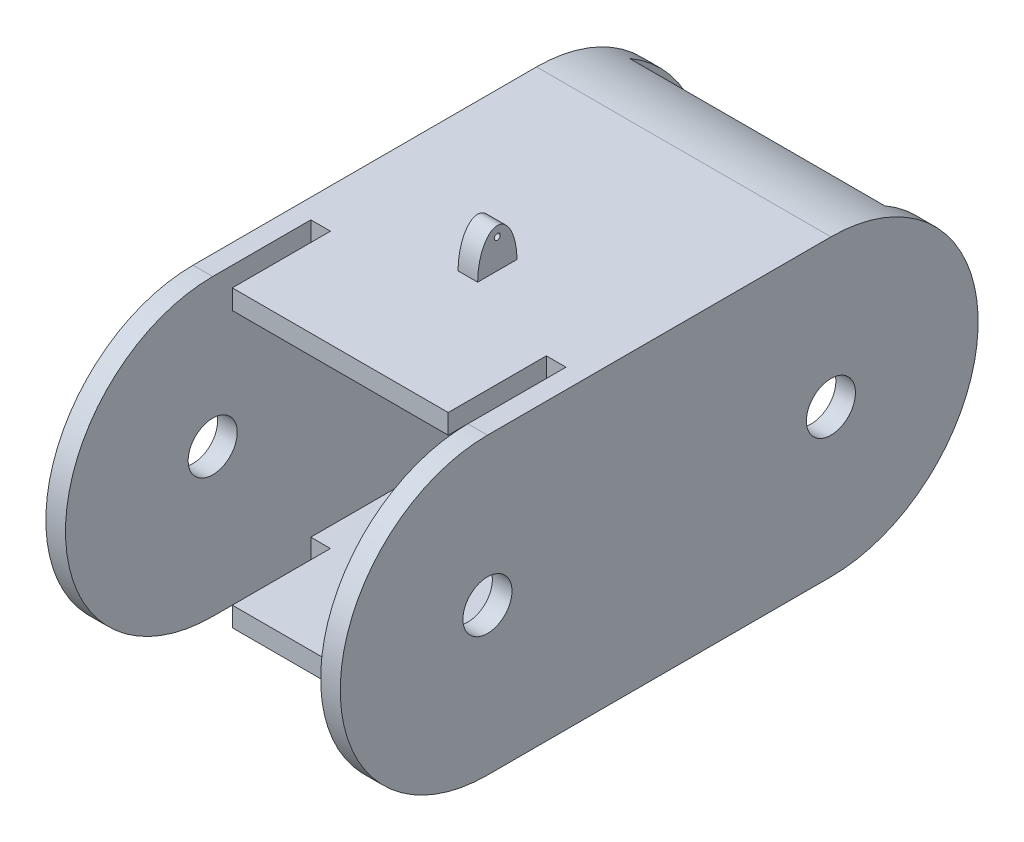
SolidWorks part; units mm, degrees
ref_plane "Front Plane" through (0, 0, 0) normal (0, 0, 1) x (1, 0, 0)
ref_plane "Top Plane" through (0, 0, 0) normal (0, 1, 0) x (1, 0, 0)
ref_plane "Right Plane" through (0, 0, 0) normal (1, 0, 0) x (0, 0, -1)
ref_plane "End Plane" through (0, 0, -31.75) normal (0, 0, 1) x (1, 0, 0)
ref_plane "Inside Plane" through (0, 19.05, 0) normal (0, 1, 0) x (1, 0, 0)
sketch "Sketch1" plane through (0, 0, 0) normal (0, 1, 0) x (1, 0, 0)
  line L1 (0, 0) -> (19.05, 0)
  line L2 (0, 0) -> (0, 41.275)
  line L3 (0, 41.275) -> (19.05, 41.275)
  line L4 (19.05, 0) -> (19.05, 41.275)
  dimension "D1" = 41.275
  dimension "D2" = 19.05
extrude "Boss-Extrude1" add sketch "Sketch1" along normal blind 19.05
sketch "Sketch2" plane through (0, 0, 0) normal (0, 0, 1) x (1, 0, 0)
  line L0 (0, 19.05) -> (19.05, 19.05) construction
  line L1 (1.27, 17.78) -> (17.78, 17.78)
  line L2 (1.27, 17.78) -> (1.27, 1.27)
  line L3 (1.27, 1.27) -> (17.78, 1.27)
  line L4 (17.78, 17.78) -> (17.78, 1.27)
  line L5 (0, 19.05) -> (0, 0) construction
  line L6 (0, 0) -> (19.05, 0) construction
  line L7 (19.05, 19.05) -> (19.05, 0) construction
  dimension "D1" = 1.27
  dimension "D2" = 1.27
  dimension "D3" = 1.27
  dimension "D4" = 1.27
extrude "Cut-Extrude1" cut sketch "Sketch2" against normal blind 50.8
sketch "Sketch3" plane through (0, 19.05, 0) normal (0, 1, 0) x (1, 0, 0)
  line L0 (0, 41.275) -> (0, 0) construction
  line L1 (8.89, 20.32) -> (10.16, 20.32)
  line L2 (8.89, 20.32) -> (8.89, 17.78)
  line L3 (8.89, 17.78) -> (10.16, 17.78)
  line L4 (10.16, 20.32) -> (10.16, 17.78)
  line L5 (0, 0) -> (19.05, 0) construction
  dimension "D1" = 1.27
  dimension "D2" = 8.89
  dimension "D3" = 17.78
  dimension "D4" = 2.54
extrude "Boss-Extrude2" add sketch "Sketch3" along normal blind 2.54
sketch "Sketch4" plane through (0, 0, 0) normal (1, 0, 0) x (0, 0, -1)
  line L0 (20.32, 19.05) -> (17.78, 19.05) construction
  line L1 (19.05, 21.59) -> (19.05, 20.955) construction
  line L2 (41.275, 19.05) -> (0, 19.05) construction
  line L4 (41.275, 0) -> (0, 0) construction
  line L5 (0, 19.05) -> (0, 0) construction
  circle A0 centre (19.05, 20.955) radius 0.1905
  arc A1 (20.32, 19.05) -> (17.78, 19.05) centre (19.05, 20.4483) ccw
  circle A4 centre (9.525, 9.525) radius 1.5875
  arc A6 (9.525, 19.05) -> (9.525, 0) centre (9.525, 9.525) ccw
  arc A7 (9.525, 19.05) -> (9.525, 0) centre (4.0998, 9.525) ccw
  ellipse E0 centre (19.05, 19.05) end of major axis (19.05, 21.59) minor radius 1.27 (20.32, 19.05) -> (17.78, 19.05) ccw
  dimension "D1" = 0.635
  dimension "D4" = 9.525
  dimension "D5" = 9.525
extrude "Cut-Extrude2" cut sketch "Sketch4" along normal blind 19.05
fillet "Fillet1" [suppressed] radius 0.635
fillet "Fillet2" [suppressed] radius 2.54
ref_plane "Mirror Plane" through (0, 0, -20.6375) normal (0, 0, 1) x (1, 0, 0)
mirror "Mirror1" about plane through (0, 0, -20.6375) normal (0, 0, 1) of "Cut-Extrude2"
sketch "Sketch7" plane through (0, 19.05, 0) normal (0, 1, 0) x (1, 0, 0)
  line L0 (2.54, 9.525) -> (16.51, 9.525)
  line L1 (1.27, 0) -> (2.54, 0)
  line L2 (1.27, 0) -> (1.27, 15.875)
  line L3 (1.27, 15.875) -> (2.54, 15.875)
  line L4 (2.54, 9.525) -> (2.54, 15.875)
  line L5 (17.78, 0) -> (16.51, 0)
  line L6 (17.78, 0) -> (17.78, 15.875)
  line L7 (17.78, 15.875) -> (16.51, 15.875)
  line L8 (16.51, 9.525) -> (16.51, 15.875)
  line L9 (19.05, 9.525) -> (0, 9.525) construction
  line L10 (2.54, 0) -> (16.51, 0)
  dimension "D1" = 1.27
  dimension "D2" = 1.27
  dimension "D3" = 15.875
  dimension "D4" = 15.875
extrude "Cut-Extrude3" cut sketch "Sketch7" against normal blind 25.4
